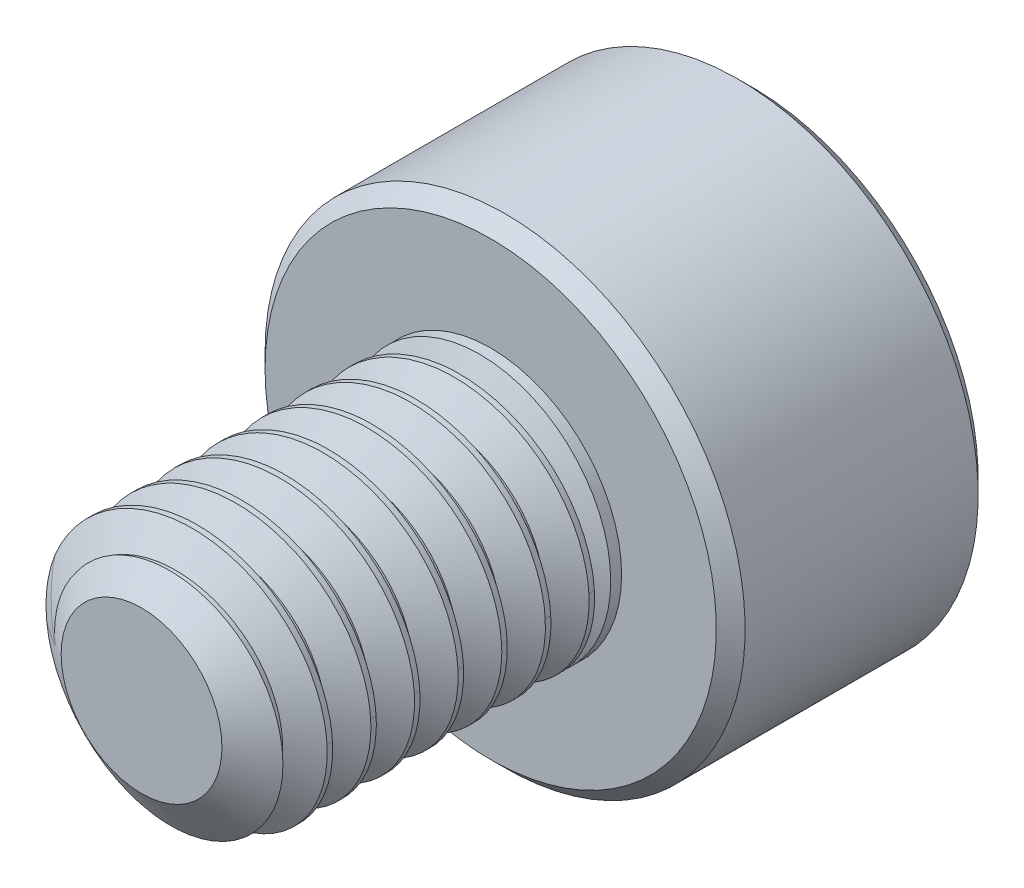
SolidWorks part; units mm, degrees
ref_plane "Front Plane" through (0, 0, 0) normal (0, 0, 1) x (1, 0, 0)
ref_plane "Top Plane" through (0, 0, 0) normal (0, 1, 0) x (1, 0, 0)
ref_plane "Right Plane" through (0, 0, 0) normal (1, 0, 0) x (0, 0, -1)
sketch "Sketch1" plane through (0, 0, 0) normal (0, 0, 1) x (1, 0, 0)
  circle A0 centre (0, 0) radius 1.5
  dimension "OD" = 3
extrude "Extrude1" add sketch "Sketch1" against normal blind 4
sketch "Sketch2" plane through (0, 0, 0) normal (0, 0, 1) x (1, 0, 0)
  circle A0 centre (0, 0) radius 1.5 construction
  circle A1 centre (0, 0) radius 1.5
curve "Helix/Spiral1" pitch 0.5 height 4.5 radius 1.5 centre (0, 0, 0) axis (0, 0, -1) start towards (0, 1, 0) parameters "pitch"=0.5
sketch "Sketch3" plane through (0, 0, 0) normal (1, 0, 0) x (0, 0, -1)
  line L0 (-0.4375, 1.5) -> (-0.25, 1.1752)
  line L1 (-0.25, 1.1752) -> (-0.1875, 1.1752)
  line L2 (-0.1875, 1.1752) -> (0, 1.5)
  line L3 (-0.4375, 1.5) -> (0, 1.5)
  line L4 (-0.2187, 1.5) -> (-0.2187, 1.1752) construction
  line L5 (-0.3437, 1.3376) -> (-0.0937, 1.3376) construction
  line L6 (0, 1.5) -> (0, -1.5) construction
  line L7 (0, -1.5) -> (4, -1.5) construction
  point P11 (2.25, -1.5)
  dimension "D1" = 0.0625
  dimension "D2" = 0.25
  dimension "D3" = 60
  dimension "D4" = 2.25
sweep "Cut-Sweep1" cut profiles "Sketch3" path "Helix/Spiral1" align with end faces yes
sketch "Sketch4" plane through (0, 0, 0) normal (1, 0, 0) x (0, 0, -1)
  line L0 (0.4053, 1.5) -> (0, 0.9212)
  line L1 (0, 0.9212) -> (0, 1.5)
  line L2 (0.4053, 1.5) -> (0, 1.5)
  line L3 (-0.4375, 1.5) -> (0, 1.5) construction
  line L4 (0, 0) -> (7.0209, 0) construction
  dimension "D1" = 55
  dimension "D2" = 0.254
revolve "Cut-Revolve1" cut sketch "Sketch4" angle 360 about L4
sketch "Sketch5" plane through (0, 0, 0) normal (1, 0, 0) x (0, 0, -1)
  line L0 (4, -1.1822) -> (4, 1.0703) construction
  line L1 (4, 1.5) -> (0.1203, 1.5)
  line L2 (4, 1.5) -> (4, 0)
  line L3 (4, 0) -> (0.0001, 0)
  line L4 (0.0001, 1.1698) -> (0.0001, 0)
  line L5 (0.1203, 1.5) -> (0.0001, 1.1698)
  line L6 (0, 0) -> (9.9695, 0) construction
  point P3 (0.0001, 1.5)
  point P10 (0.0001, 1.5)
  dimension "D1" = 0.3302
  dimension "Thread min" = 0.0001
  dimension "D3" = 20
revolve "partially thread" [suppressed] add sketch "Sketch5" angle 360 about L6
sketch "Sketch6" plane through (0, 0, -4) normal (0, 0, -1) x (-1, 0, 0)
  circle A0 centre (0, 0) radius 2.75
  dimension "head dia" = 5.5
extrude "Extrude2" add sketch "Sketch6" along normal blind 3
sketch "Sketch7" plane through (0, 0, -7) normal (0, 0, -1) x (-1, 0, 0)
  line L1 (0, 1.4434) -> (-1.25, 0.7217)
  line L2 (-1.25, 0.7217) -> (-1.25, -0.7217)
  line L3 (-1.25, -0.7217) -> (0, -1.4434)
  line L4 (0, -1.4434) -> (1.25, -0.7217)
  line L5 (1.25, -0.7217) -> (1.25, 0.7217)
  line L6 (1.25, 0.7217) -> (0, 1.4434)
  circle A0 centre (0, 0) radius 1.25 construction
  dimension "hex dia" = 2.5
extrude "Cut-Extrude1" cut sketch "Sketch7" against normal blind 1.875
sketch "Sketch8" plane through (0, 0, -7) normal (0, 0, -1) x (-1, 0, 0)
  circle A0 centre (0, 0) radius 1.4434
extrude "Cut-Extrude2" cut sketch "Sketch8" against normal through all draft 45
chamfer "Chamfer1" distance 0.165 angle 45 2 edges at (-2.75, 0, -7) (-2.75, 0, -4)
sketch "Sketch9" plane through (0, 0, 0) normal (1, 0, 0) x (0, 0, -1)
  line L0 (0, 1.5) -> (0, -1.5) construction
  line L1 (2.75, 1.5) -> (2.75, -1.5) construction
  dimension "D1" = 2.75
sketch "Sketch10" plane through (0, 0, 0) normal (1, 0, 0) x (0, 0, -1)
  line L0 (4, 1.5) -> (4, 0)
  line L1 (4, 1.5) -> (3.875, 1.5)
  line L2 (3.875, 1.5) -> (3.2537, 0)
  line L3 (4, 0) -> (3.2537, 0)
  line L4 (4, 2.585) -> (4, -2.585) construction
  dimension "D1" = 22.5
  dimension "D2" = 0.125
revolve "Revolve1" add sketch "Sketch10" angle 360 about L3
equation "\"D3@Helix/Spiral1\" = \"screw length@Extrude1\"+\"pitch@Helix/Spiral1\""
equation "\"D1@Sketch3\" = \"pitch@Helix/Spiral1\"*.125"
equation "\"D2@Sketch3\" = \"pitch@Helix/Spiral1\"*.5"
equation "\"D1@Cut-Extrude1\" = \"hex dia@Sketch7\"*.75"
equation "\"D1@Chamfer1\" = \"head dia@Sketch6\"*.03"
equation "\"D1@Sketch9\" = \"pitch@Helix/Spiral1\"*5.5"
equation "\"D2@Sketch10\" = \"pitch@Helix/Spiral1\"*.25"
equation "\"D4@Sketch3\" = \"pitch@Helix/Spiral1\"*4.50"
